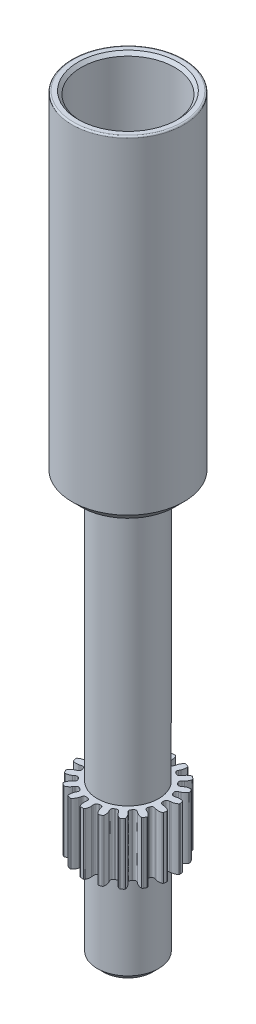
SolidWorks part; units mm, degrees
ref_plane "Front Plane" through (0, 0, 0) normal (0, 0, 1) x (1, 0, 0)
ref_plane "Top Plane" through (0, 0, 0) normal (0, 1, 0) x (1, 0, 0)
ref_plane "Right Plane" through (0, 0, 0) normal (1, 0, 0) x (0, 0, -1)
sketch "Sketch1" plane through (0, 0, 0) normal (0, 0, 1) x (1, 0, 0)
  line L0 (0, 0) -> (-10, 0)
  line L1 (-10, 0) -> (-10, 135)
  line L2 (-10, 135) -> (-18.25, 135)
  line L3 (-18.25, 135) -> (-18.25, 245)
  line L4 (-18.25, 245) -> (-15.25, 245)
  line L5 (-15.25, 245) -> (-15.25, 155)
  line L6 (-15.25, 155) -> (0, 155)
  line L7 (0, 155) -> (0, 0)
  line L8 (-7.3324, 35) -> (8.884, 35) construction
  point P11 (-18, 69.8613)
  dimension "D1" = 110
  dimension "D2" = 135
  dimension "D4" = 15.25
  dimension "D5" = 10
  dimension "D6" = 90
  dimension "D7" = 3
revolve "Revolve1" add sketch "Sketch1" angle 360 about L7
chamfer "Chamfer1" distance 3 angle 45 1 edges at (-18.25, 135, 0)
fillet "Fillet1" radius 0.5 1 edges at (-18.25, 245, 0)
ref_axis "Axis1" through (0, 155, 0) along (0, 1, 0)
chamfer "Chamfer2" distance 1 angle 45 1 edges at (-15.25, 245, 0)
ref_plane "Plane1" through (0, 30, 0) normal (0, -1, 0) x (-1, 0, 0)
sketch "Sketch2" plane through (0, 30, 0) normal (0, -1, 0) x (-1, 0, 0)
  line L0 (0, 0) -> (0, 50.5669) construction
  line L1 (0, 0) -> (-2.3642, 54.1494) construction
  line L2 (0, 0) -> (-4.5793, 52.3414) construction
  line L3 (0, 0) -> (-8.4968, 48.1875) construction
  line L16 (-1.133, 12.9505) -> (-1.0023, 11.4562)
  line L17 (-1.997, 11.3253) -> (0, 0)
  line L18 (1.997, 11.3253) -> (0, 0)
  line L19 (1.133, 12.9505) -> (1.0023, 11.4562)
  arc A0 (0.4277, 14.9939) -> (-0.4277, 14.9939) centre (0, 0) ccw
  circle A1 centre (0, 0) radius 13
  arc A2 (0.7715, 14.778) -> (1.133, 12.9505) centre (-2.1947, 13.2417) cw
  circle A3 centre (0, 0) radius 11.5
  arc A6 (-0.7715, 14.778) -> (-1.133, 12.9505) centre (2.1947, 13.2417) ccw
  arc A7 (-1.3073, 14.9429) -> (6.9708, 13.2818) centre (0, 0) ccw
  arc A8 (-0.7715, 14.778) -> (-0.4277, 14.9939) centre (-0.4163, 14.5941) cw
  arc A9 (0.7715, 14.778) -> (0.4277, 14.9939) centre (0.4163, 14.5941) ccw
  point P25 (0, 0)
  point P36 (-0.6543, 14.9857)
  point P39 (0.6543, 14.9857)
  dimension "D1" = 30
  dimension "D2" = 26
  dimension "D3" = 23
  dimension "D5" = 2.5
  dimension "D8" = 0.4
  dimension "D6" = 5
  dimension "D7" = 10
extrude "Boss-Extrude1" add sketch "Sketch2" against normal blind 20 contours A3 L17 L18 | A3 L19 A1 L16 | A0 A6 A1 A2 region at (0, 30, -12.2497) region at (0, 30, -13.9056) region at (0, 30, -7.6278)
fillet "Fillet2" radius 1 2 edges at (1.0023, 40, -11.4562) (-1.0023, 40, -11.4562) curvature continuous yes
pattern_circular "CirPattern2" count 18 over 360 about axis through (0, 155, 0) along (0, 1, 0) of "Fillet2", "Boss-Extrude1"
chamfer "Chamfer3" distance 2 angle 45 1 edges at (-10, 0, 0)
ref_plane "Plane2" through (0, 80, 0) normal (0, 1, 0) x (1, 0, 0)
